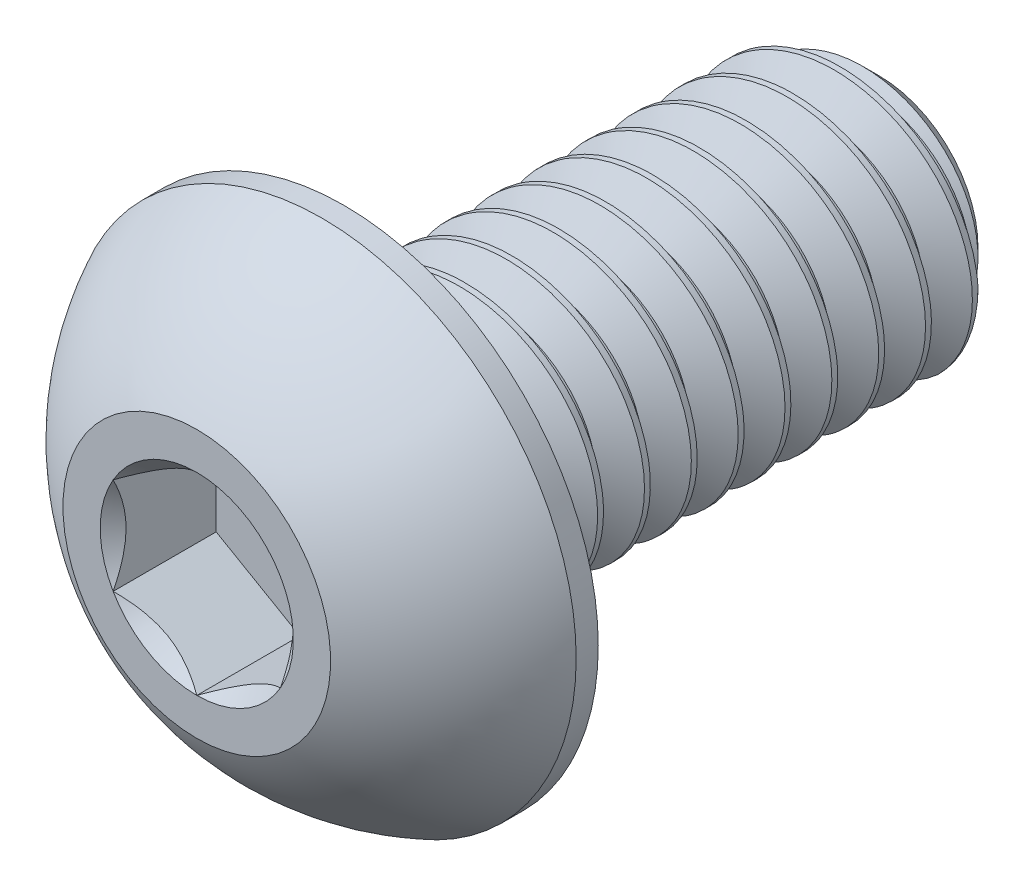
SolidWorks part; units mm, degrees
ref_plane "Front" through (0, 0, 0) normal (0, 0, 1) x (1, 0, 0)
ref_plane "Top" through (0, 0, 0) normal (0, 1, 0) x (1, 0, 0)
ref_plane "Right" through (0, 0, 0) normal (1, 0, 0) x (0, 0, -1)
sketch "Sketch1" plane through (0, 0, 0) normal (1, 0, 0) x (0, 0, -1)
  line L2 (2.2, 2) -> (10.2, 2)
  line L3 (10.2, 2) -> (10.2, 0)
  line L4 (10.2, 0) -> (2.2, 0)
  line L6 (1.87, 3.8) -> (2.2, 3.8) construction
  line L7 (10.2, 2) -> (10.2, -2) construction
  line L8 (0, 0) -> (2.2, 0) construction
  line L9 (2.2, 3.8) -> (2.2, -3.8) construction
  line L11 (2.2, 2) -> (2.2, 0)
  line L13 (0, 1.25) -> (0, -1.25) construction
  line L14 (0, 1.25) -> (0, 2) construction
  arc A3 (0, 2) -> (1.87, 3.8) centre (3.7264, 0) cw construction
  dimension "D1" = 0.33
revolve "Revolve1" add sketch "Sketch1" angle 360 mid plane about L4
sketch "Sketch3" plane through (0, 0, -10.2) normal (0, 0, -1) x (-1, 0, 0)
  circle A0 centre (0, 0) radius 2
curve "Helix/Spiral1" pitch 0.7 height 8.7 radius 2 centre (0, 0, -10.2) axis (0, 0, 1) start towards (0, 1, 0)
sketch "Sketch2" plane through (0, 0, 0) normal (1, 0, 0) x (0, 0, -1)
  line L0 (10.2, 2) -> (10.8125, 2)
  line L1 (10.8125, 2) -> (10.55, 1.5453)
  line L2 (10.55, 1.5453) -> (10.4625, 1.5453)
  line L3 (10.4625, 1.5453) -> (10.2, 2)
  line L4 (10.3313, 1.7727) -> (10.6813, 1.7727) construction
  dimension "D1" = 60
  dimension "D2" = 0.0875
  dimension "D3" = 0.35
chamfer "Chamfer1" distance 0.525 angle 45 1 edges at (0, 2, -10.2)
sweep "Cut-Sweep1" cut profiles "Sketch2" path "Helix/Spiral1" align with end faces yes
sketch "Sketch7" plane through (0, 0, 0) normal (1, 0, 0) x (0, 0, -1)
  line L6 (1.87, 3.8) -> (2.2, 3.8) construction
  line L8 (0, 0) -> (2.2, 0) construction
  line L11 (2.2, 3.8) -> (2.2, -3.8) construction
  line L12 (1.87, 3.8) -> (2.2, 3.8)
  line L13 (0, 0) -> (2.2, 0)
  line L14 (0, 1.25) -> (0, -1.25) construction
  line L15 (2.2, 3.8) -> (2.2, 0)
  line L16 (0, 2) -> (0, 0)
  arc A2 (1.87, 3.8) -> (0, 2) centre (3.7264, 0) ccw construction
  arc A3 (1.87, 3.8) -> (0, 2) centre (3.7264, 0) ccw
revolve "Revolve2" add sketch "Sketch7" angle 360 mid plane about L13
sketch "Sketch5" plane through (0, 0, 0) normal (0, 0, 1) x (1, 0, 0)
  line L1 (1.25, -0.7217) -> (1.25, 0.7217)
  line L2 (1.25, 0.7217) -> (0, 1.4434)
  line L3 (0, 1.4434) -> (-1.25, 0.7217)
  line L4 (-1.25, 0.7217) -> (-1.25, -0.7217)
  line L5 (-1.25, -0.7217) -> (0, -1.4434)
  line L6 (0, -1.4434) -> (1.25, -0.7217)
  circle A0 centre (0, 0) radius 1.25 construction
extrude "Cut-Extrude2" cut sketch "Sketch5" against normal blind 1.54
sketch "Sketch6" plane through (0, 0, 0) normal (0, 0, 1) x (1, 0, 0)
  circle A0 centre (0, 0) radius 1.4434
extrude "Cut-Extrude3" cut sketch "Sketch6" against normal blind 1.54 draft 45
sketch "Sketch9" [suppressed] plane through (0, 0, -2.2) normal (0, 0, 1) x (1, 0, 0)
  circle A2 centre (0, 0) radius 2
extrude "Boss-Extrude2" [suppressed] add sketch "Sketch9" against normal offset from surface (5 mm away) 28.575 up to face at (0, 1.475, -10.2)
sketch "Sketch10" plane through (0, 0, 0) normal (1, 0, 0) x (0, 0, -1)
  line L0 (10.2, 2) -> (10.2, -2) construction
  point P0 (9.15, -2)
  dimension "D1" = 1.05
equation "\"D3@Helix/Spiral1\" = \"Lg@Sketch1\" + \"D4@Helix/Spiral1\""
equation "\"D2@Sketch2\" = \"D4@Helix/Spiral1\" * .125"
equation "\"D3@Sketch2\" = \"D4@Helix/Spiral1\" * .5"
equation "\"D1@Chamfer1\" = \"D4@Helix/Spiral1\" * .75"
equation "\"D1@Cut-Extrude2\" = \"Head Ht@Sketch1\" * .7"
equation "\"D1@Sketch1\" = \"Head Ht@Sketch1\" * .15"
equation "\"D1@Sketch10\" = \"D4@Helix/Spiral1\" * 1.5"
equation "\"D1@Cut-Extrude3\" = \"D1@Cut-Extrude2\""
